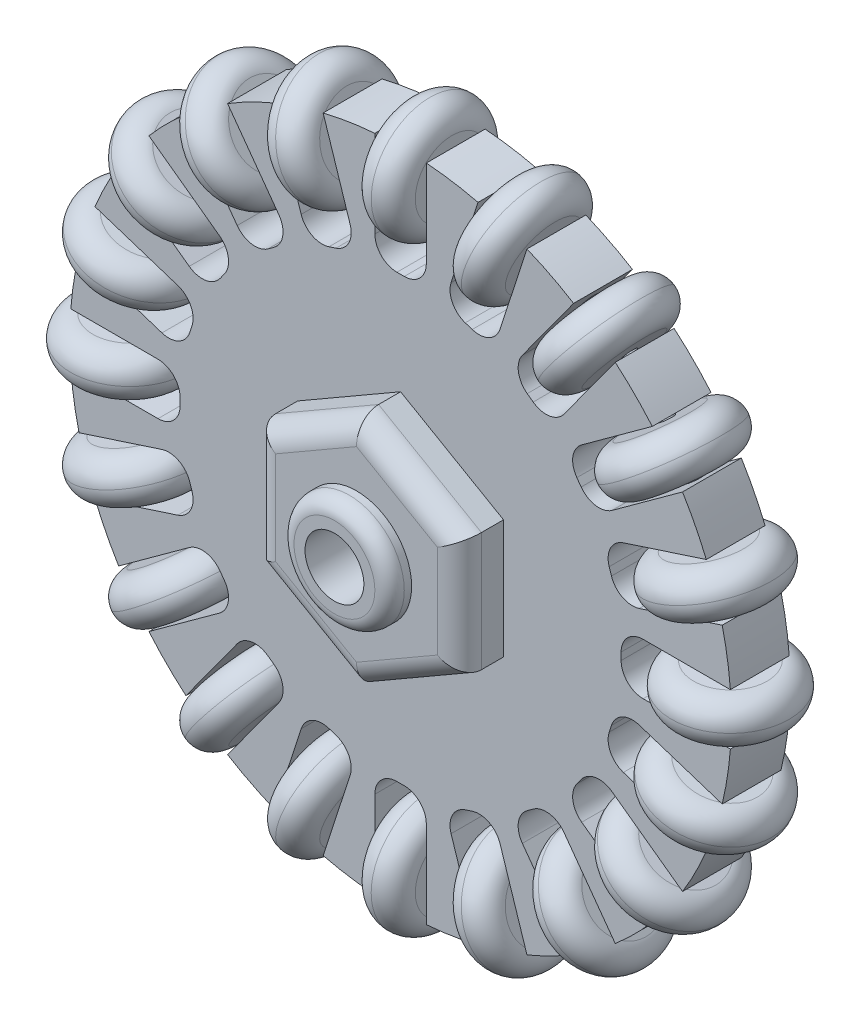
SolidWorks part; units mm, degrees
ref_plane "Front Plane" through (0, 0, 0) normal (0, 0, 1) x (1, 0, 0)
ref_plane "Top Plane" through (0, 0, 0) normal (0, 1, 0) x (1, 0, 0)
ref_plane "Right Plane" through (0, 0, 0) normal (1, 0, 0) x (0, 0, -1)
sketch "Sketch1" plane through (0, 0, 0) normal (0, 0, 1) x (1, 0, 0)
  circle A0 centre (0, 0) radius 22.5
  dimension "D1" = 45
extrude "Boss-Extrude1" add sketch "Sketch1" along normal blind 2 and the other way blind 2
sketch "Sketch2" plane through (0, 0, 2) normal (0, 0, 1) x (1, 0, 0)
  line L0 (0, 22.5) -> (0, 0) construction
  line L1 (-1.75, 30) -> (1.75, 30)
  line L2 (-1.75, 30) -> (-1.75, 16.5)
  line L3 (-0.25, 15) -> (0.25, 15)
  line L4 (1.75, 30) -> (1.75, 16.5)
  line L5 (-1.75, 30) -> (1.75, 15) construction
  line L6 (-1.75, 15) -> (1.75, 30) construction
  circle A0 centre (0, 0) radius 22.5 construction
  arc A1 (0.25, 15) -> (1.75, 16.5) centre (0.25, 16.5) ccw
  arc A2 (-1.75, 16.5) -> (-0.25, 15) centre (-0.25, 16.5) ccw
  point P0 (0, 22.5)
  point P7 (0, 22.5)
  dimension "D3" = 1.5
  dimension "D1" = 3.5
  dimension "D2" = 15
extrude "Cut-Extrude1" cut sketch "Sketch2" against normal through all
pattern_circular "CirPattern1" count 20 over 360 about axis through (0, 0, 2) along (0, 0, 1) of "Cut-Extrude1"
sketch "Sketch3" plane through (0, 0, 0) normal (0, 0, 1) x (1, 0, 0)
  circle A0 centre (0, 0) radius 21
  dimension "D1" = 42
sweep "Sweep1" add path "Sketch3" circular profile diameter 1 parameters "D3"=1
sketch "Sketch8" plane through (0, 0, 0) normal (1, 0, 0) x (0, 0, -1)
  line L0 (0, 22.4318) -> (0, 20.4318) construction
  line L1 (-2, 22.4318) -> (2, 22.4318) construction
  circle A0 centre (0, 20.4318) radius 4
  dimension "D2" = 8
  dimension "D1" = 2
extrude "Boss-Extrude2" add sketch "Sketch8" along normal blind 1.5 and the other way blind 1.5
fillet "Fillet1" radius 1.5 2 edges at (1.5, 20.4318, -4) (-1.5, 20.4318, -4)
pattern_circular "CirPattern3" count 20 over 360 about axis through (0, 0, 2) along (0, 0, 1) of "Boss-Extrude2", "Fillet1"
sketch "Sketch15" plane through (0, 0, 2) normal (0, 0, 1) x (1, 0, 0)
  line L1 (0, 8.0829) -> (-7, 4.0415)
  line L2 (-7, 4.0415) -> (-7, -4.0415)
  line L3 (-7, -4.0415) -> (0, -8.0829)
  line L4 (0, -8.0829) -> (7, -4.0415)
  line L5 (7, -4.0415) -> (7, 4.0415)
  line L6 (7, 4.0415) -> (0, 8.0829)
  circle A0 centre (0, 0) radius 7 construction
  dimension "D1" = 14
extrude "Boss-Extrude3" add sketch "Sketch15" along normal blind 3
sketch "Sketch16" plane through (0, 0, 5) normal (0, 0, 1) x (1, 0, 0)
  circle A0 centre (0, 0) radius 3.75
  dimension "D1" = 7.5
extrude "Boss-Extrude4" add sketch "Sketch16" along normal blind 1.5
fillet "Fillet2" radius 1.5 6 edges at (-3.5, -6.0622, 5) (3.5, -6.0622, 5) (7, 0, 5) (3.5, 6.0622, 5) (-3.5, 6.0622, 5) (-7, 0, 5)
sketch "Sketch17" plane through (0, 0, -2) normal (0, 0, -1) x (-1, 0, 0)
  line L1 (7, -4.0415) -> (7, 4.0415)
  line L2 (7, 4.0415) -> (0, 8.0829)
  line L3 (0, 8.0829) -> (-7, 4.0415)
  line L4 (-7, 4.0415) -> (-7, -4.0415)
  line L5 (-7, -4.0415) -> (0, -8.0829)
  line L6 (0, -8.0829) -> (7, -4.0415)
  circle A0 centre (0, 0) radius 7 construction
  dimension "D1" = 14
extrude "Boss-Extrude5" add sketch "Sketch17" along normal blind 5
sketch "Sketch18" plane through (0, 0, -7) normal (0, 0, -1) x (-1, 0, 0)
  circle A0 centre (0, 0) radius 2
  dimension "D1" = 4
extrude "Cut-Extrude2" cut sketch "Sketch18" against normal through all
fillet "Fillet3" radius 1 1 edges at (3.75, 0, 6.5)
